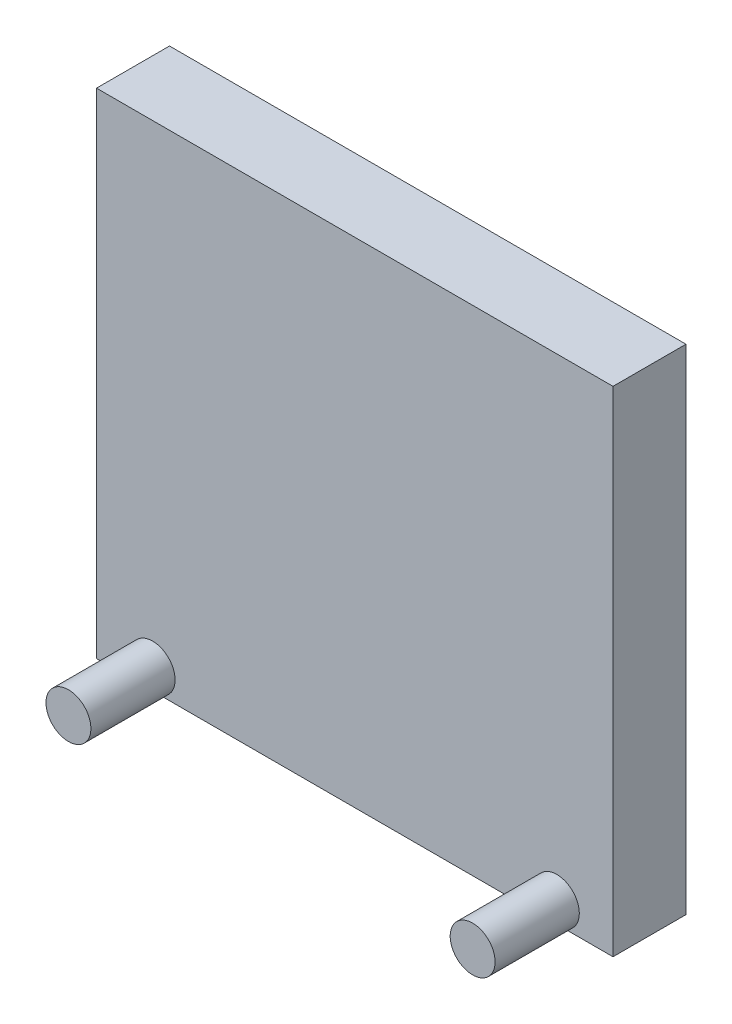
SolidWorks part; units mm, degrees
ref_plane "Front Plane" through (0, 0, 0) normal (0, 0, 1) x (1, 0, 0)
ref_plane "Top Plane" through (0, 0, 0) normal (0, 1, 0) x (1, 0, 0)
ref_plane "Right Plane" through (0, 0, 0) normal (1, 0, 0) x (0, 0, -1)
sketch "Sketch1" plane through (0, 0, 0) normal (0, 0, 1) x (1, 0, 0)
  line L0 (114.291, -675.7503) -> (200.291, -675.7503) construction
  line L1 (108.291, -679.4503) -> (200.291, -679.4503)
  line L2 (108.291, -679.4503) -> (108.291, -591.4503)
  line L3 (108.291, -591.4503) -> (200.291, -591.4503)
  line L4 (200.291, -679.4503) -> (200.291, -591.4503)
  line L5 (108.291, -679.4503) -> (200.291, -679.4503)
  line L6 (108.291, -679.4503) -> (108.291, -668.4503)
  line L7 (108.291, -668.4503) -> (200.291, -668.4503)
  line L8 (200.291, -679.4503) -> (200.291, -668.4503)
  line L9 (118.291, -675.7503) -> (136.291, -675.7503) construction
  line L10 (136.291, -675.7503) -> (154.291, -675.7503) construction
  line L11 (154.291, -675.7503) -> (172.291, -675.7503) construction
  line L12 (172.291, -675.7503) -> (190.291, -675.7503) construction
  line L13 (108.291, -679.4503) -> (200.291, -679.4503)
  line L14 (108.291, -679.4503) -> (108.291, -686.4503)
  line L15 (200.291, -679.4503) -> (200.291, -686.4503)
  line L16 (108.291, -686.4503) -> (200.291, -686.4503)
  line L17 (200.291, -686.4503) -> (200.291, -591.4503)
  line L18 (200.291, -686.4503) -> (248.291, -686.4503)
  line L19 (200.291, -591.4503) -> (248.291, -591.4503)
  line L20 (248.291, -686.4503) -> (248.291, -591.4503)
  circle A0 centre (118.291, -675.7503) radius 4
  circle A4 centre (190.291, -675.7503) radius 4
  dimension "D2" = 8
  dimension "D3" = 48
  dimension "D8" = 7
  dimension "D9" = 10.7
  dimension "D1" = 92
  dimension "D4" = 88
  dimension "D5" = 11
  dimension "D6" = 10
  dimension "D7" = 10
extrude "Boss-Extrude1" add sketch "Sketch1" against normal blind 6.5 rebuild error yes
extrude "Boss-Extrude2" add sketch "Sketch1<3>" along normal blind 15 contours A0 | A4
sketch "Sketch1<3>" plane through (0, 0, 0) normal (0, 0, 1) x (1, 0, 0) same geometry as "Sketch1"
chamfer "Chamfer2" distance 3 angle 45 rebuild error yes
chamfer "Chamfer3" distance 3 angle 45 rebuild error yes
chamfer "Chamfer4" distance 3 angle 45 rebuild error yes
mirror "Mirror1" rebuild error yes
extrude "Boss-Extrude3" add sketch "Sketch1<4>" against normal blind 13 separate body contours L2 L7 L4 L3 | L7 L2 L1 L4 A4 A0 region at (154.291, -673.7596, 0) region at (154.291, -629.9503, 0)
sketch "Sketch1<4>" plane through (0, 0, 0) normal (0, 0, 1) x (1, 0, 0) same geometry as "Sketch1"
sketch "Sketch8" plane through (0, 0, 0) normal (0, 0, -1) x (-1, 0, 0)
  line L4 (-108.291, -679.4503) -> (-108.291, -591.4503)
  line L5 (-108.291, -591.4503) -> (-200.291, -591.4503)
  line L6 (-200.291, -591.4503) -> (-200.291, -679.4503)
  line L7 (-200.291, -679.4503) -> (-191.8109, -679.4503)
  line L8 (-108.291, -679.4503) -> (-108.291, -591.4503)
  line L9 (-108.291, -591.4503) -> (-200.291, -591.4503)
  line L10 (-200.291, -591.4503) -> (-200.291, -679.4503)
  line L11 (-200.291, -679.4503) -> (-191.8109, -679.4503)
  line L14 (-188.7712, -679.4503) -> (-119.8109, -679.4503)
  line L15 (-188.7712, -679.4503) -> (-119.8109, -679.4503)
  line L16 (-116.7712, -679.4503) -> (-108.291, -679.4503)
  line L17 (-116.7712, -679.4503) -> (-108.291, -679.4503)
  circle A0 centre (-190.291, -675.7503) radius 4 construction
  circle A1 centre (-190.291, -675.7503) radius 4
  circle A2 centre (-118.291, -675.7503) radius 4 construction
  circle A3 centre (-118.291, -675.7503) radius 4
  arc A6 (-188.7712, -679.4503) -> (-191.8109, -679.4503) centre (-190.291, -675.7503) ccw
  arc A7 (-188.7712, -679.4503) -> (-191.8109, -679.4503) centre (-190.291, -675.7503) ccw
  arc A8 (-116.7712, -679.4503) -> (-119.8109, -679.4503) centre (-118.291, -675.7503) ccw
  arc A9 (-116.7712, -679.4503) -> (-119.8109, -679.4503) centre (-118.291, -675.7503) ccw
  dimension "D1" = 0
extrude "Boss-Extrude4" add sketch "Sketch8" along normal through all contours A1 | A3
